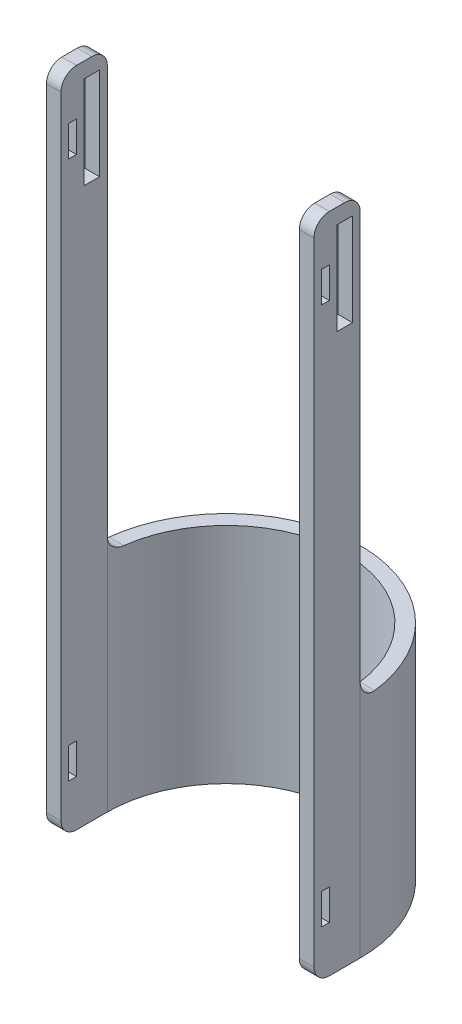
SolidWorks part; units mm, degrees
other "Markup1"
sketch "Sketch11" plane through (-75, 302.2666, -81.3292) normal (-0.1024, 0.768, -0.6322) x (-0.9876, -0.0025, 0.157)
material "PE High Density"
ref_plane "Front Plane" through (0, 0, 0) normal (0, 0, 1) x (1, 0, 0)
ref_plane "Top Plane" through (0, 0, 0) normal (0, 1, 0) x (1, 0, 0)
ref_plane "Right Plane" through (0, 0, 0) normal (1, 0, 0) x (0, 0, -1)
sketch "Sketch1" plane through (0, 0, 0) normal (0, 1, 0) x (1, 0, 0)
  line L0 (-86.724, 0) -> (86.724, 0) construction
  line L1 (-77.2727, 0) -> (-86.724, 0)
  line L2 (86.724, 0) -> (77.2727, 0)
  arc A0 (86.724, 0) -> (-86.724, 0) centre (0, 0) ccw
  arc A1 (77.2727, 0) -> (-77.2727, 0) centre (0, 0) ccw
  dimension "D1" = 77.2727
  dimension "D2" = 86.724
extrude "Boss-Extrude1" add sketch "Sketch1" along normal blind 145.0115
sketch "Sketch2" plane through (0, 0, 0) normal (0, 0, 1) x (1, 0, 0)
  line L1 (77.2727, 145.0115) -> (86.724, 145.0115)
  line L2 (77.2727, 145.0115) -> (77.2727, 0)
  line L3 (77.2727, 0) -> (86.724, 0)
  line L4 (86.724, 145.0115) -> (86.724, 0)
  line L5 (-86.724, 145.0115) -> (-77.2727, 145.0115)
  line L6 (-86.724, 145.0115) -> (-86.724, 0)
  line L7 (-86.724, 0) -> (-77.2727, 0)
  line L8 (-77.2727, 145.0115) -> (-77.2727, 0)
extrude "Boss-Extrude2" add sketch "Sketch2" along normal blind 30
sketch "Sketch3" plane through (0, 145.0115, 0) normal (0, 1, 0) x (1, 0, 0)
  line L1 (-77.2727, -30) -> (-86.724, -30)
  line L2 (-77.2727, -30) -> (-77.2727, 0)
  line L3 (-77.2727, 0) -> (-86.724, 0)
  line L4 (-86.724, -30) -> (-86.724, 0)
  line L5 (86.724, -30) -> (77.2727, -30)
  line L6 (86.724, -30) -> (86.724, 0)
  line L7 (86.724, 0) -> (77.2727, 0)
  line L8 (77.2727, -30) -> (77.2727, 0)
extrude "Boss-Extrude3" add sketch "Sketch3" along normal blind 284.3485
sketch "Sketch5" plane through (-86.724, 0, 0) normal (-1, 0, 0) x (0, 0, 1)
  line L0 (0, 429.36) -> (30, 429.36) construction
  line L1 (5, 419.36) -> (15, 419.36)
  line L2 (5, 419.36) -> (5, 359.36)
  line L3 (5, 359.36) -> (15, 359.36)
  line L4 (15, 419.36) -> (15, 359.36)
  line L5 (0, 429.36) -> (0, 145.0115) construction
  dimension "D1" = 60
  dimension "D2" = 10
  dimension "D3" = 10
  dimension "D4" = 5
extrude "Cut-Extrude1" cut sketch "Sketch5" against normal blind 240
sketch "Sketch6" plane through (-86.724, 0, 0) normal (-1, 0, 0) x (0, 0, 1)
  line L0 (17.5605, 360) -> (17.5605, 300) construction
  line L1 (20, 399.36) -> (25, 399.36)
  line L2 (20, 399.36) -> (20, 379.36)
  line L3 (20, 379.36) -> (25, 379.36)
  line L4 (25, 399.36) -> (25, 379.36)
  line L5 (15, 419.36) -> (5, 419.36) construction
  line L7 (15, 359.36) -> (15, 419.36) construction
  dimension "D1" = 20
  dimension "D2" = 5
  dimension "D3" = 20
  dimension "D4" = 5
extrude "Cut-Extrude2" cut sketch "Sketch6" against normal through all
fillet "Fillet1" radius 10 4 edges at (81.9984, 429.36, 30) (-81.9984, 429.36, 30) (-81.9984, 429.36, 0) (81.9984, 429.36, 0)
fillet "Fillet2" radius 10 2 edges at (81.9984, 0, 30) (-81.9984, 0, 30)
fillet "Fillet3" radius 10 2 edges at (81.9984, 145.0115, 0) (-81.9984, 145.0115, 0)
sketch "Sketch8" plane through (-86.724, 0, 0) normal (-1, 0, 0) x (0, 0, 1)
  line L1 (20, 50) -> (25, 50)
  line L2 (20, 50) -> (20, 30)
  line L3 (20, 30) -> (25, 30)
  line L4 (25, 50) -> (25, 30)
  line L5 (20, 0) -> (0, 0) construction
  line L6 (30, 419.36) -> (30, 10) construction
  dimension "D1" = 20
  dimension "D2" = 5
  dimension "D3" = 30
  dimension "D4" = 5
extrude "Cut-Extrude3" cut sketch "Sketch8" against normal through all
ref_plane "Plane1" through (0, 80.0115, 0) normal (0, 1, 0) x (1, 0, 0)
sketch "Sketch9" plane through (0, 80.0115, 0) normal (0, 1, 0) x (1, 0, 0)
  line L0 (-26.7992, 82.4794) -> (-26.7992, 92.4794)
  line L1 (-26.7992, 92.4794) -> (26.7992, 92.4794)
  line L2 (26.7992, 92.4794) -> (26.7992, 82.4794)
  line L3 (-86.724, 0) -> (86.724, 0)
  line L4 (0, 0) -> (-26.7992, 82.4794) construction
  line L5 (0, 0) -> (26.7992, 82.4794) construction
  arc A0 (86.1455, 10) -> (-86.1455, 10) centre (0, 0) ccw construction
  arc A1 (86.724, 0) -> (-26.7992, 82.4794) centre (0, 0) ccw
  point P13 (0, 0)
  dimension "D1" = 72
  dimension "D2" = 72
  dimension "D3" = 10
  dimension "D4" = 10
extrude "Boss-Extrude4" add sketch "Sketch9" along normal mid plane 61.7166 contours A1 L2 L1 L0 region at (0, 80.0115, -88.7903)
fillet "Fillet4" radius 5 4 edges at (0, 49.1532, -92.4794) (26.7992, 80.0115, -92.4794) (-26.7992, 80.0115, -92.4794) (0, 110.8698, -92.4794)
sketch "Sketch10" plane through (0, 0, -92.4794) normal (0, 0, -1) x (-1, 0, 0)
  line L0 (21.7992, 105.8698) -> (-21.7992, 105.8698) construction
  line L1 (-21.7992, 105.8698) -> (-21.7992, 54.1532) construction
  line L2 (21.7992, 54.1532) -> (21.7992, 105.8698) construction
  line L3 (21.7992, 105.8698) -> (-21.7992, 105.8698) construction
  line L4 (-21.7992, 54.1532) -> (21.7992, 54.1532) construction
  line L5 (-21.7992, 54.1532) -> (21.7992, 54.1532) construction
  circle A0 centre (-16.7992, 100.8698) radius 1.0922
  circle A1 centre (16.7992, 100.8698) radius 1.0922
  circle A2 centre (-16.7992, 59.1532) radius 1.0922
  circle A3 centre (16.7992, 59.1532) radius 1.0922
  dimension "D1" = 2.1844
  dimension "D2" = 2.1844
  dimension "D3" = 2.1844
  dimension "D4" = 2.1844
  dimension "D5" = 5
  dimension "D7" = 5
  dimension "D8" = 5
  dimension "D9" = 5
  dimension "D10" = 5
  dimension "D11" = 5
  dimension "D12" = 5
  dimension "D6" = 5
extrude "Cut-Extrude4" cut sketch "Sketch10" against normal blind 5
cosmetic thread "Cosmetic Thread6" parameters "D2"=3.1844
cosmetic thread "Cosmetic Thread7" parameters "D2"=3.1844
cosmetic thread "Cosmetic Thread8" parameters "D2"=3.1844
cosmetic thread "Cosmetic Thread9" parameters "D2"=3.1844
equation "\"userHeight\"= 1700mm'Users height"
equation "\"shell_length\"=145.01147666"
equation "\"D1@Boss-Extrude1\"=\"shell_length\""
equation "\"partial_sidebar_length\"=284.34850000"
equation "\"shell_outer_radius\"= 86.724"
equation "\"D2@Sketch1\"=\"shell_outer_radius\""
equation "\"shell_inner_radius\"= \"userHeight\" / 22'Shell inner radius"
equation "\"D1@Sketch1\"=\"shell_inner_radius\""
equation "\"fin_platform_height\"= 51.7166 + 10"
equation "\"D1@Boss-Extrude4\"=\"fin_platform_height\""
equation "\"D1@Boss-Extrude3\"=\"partial_sidebar_length\""
equation "\"fin_platform_width\"= 43.598"
equation "\"fin_thickness\"=6.23245771"
